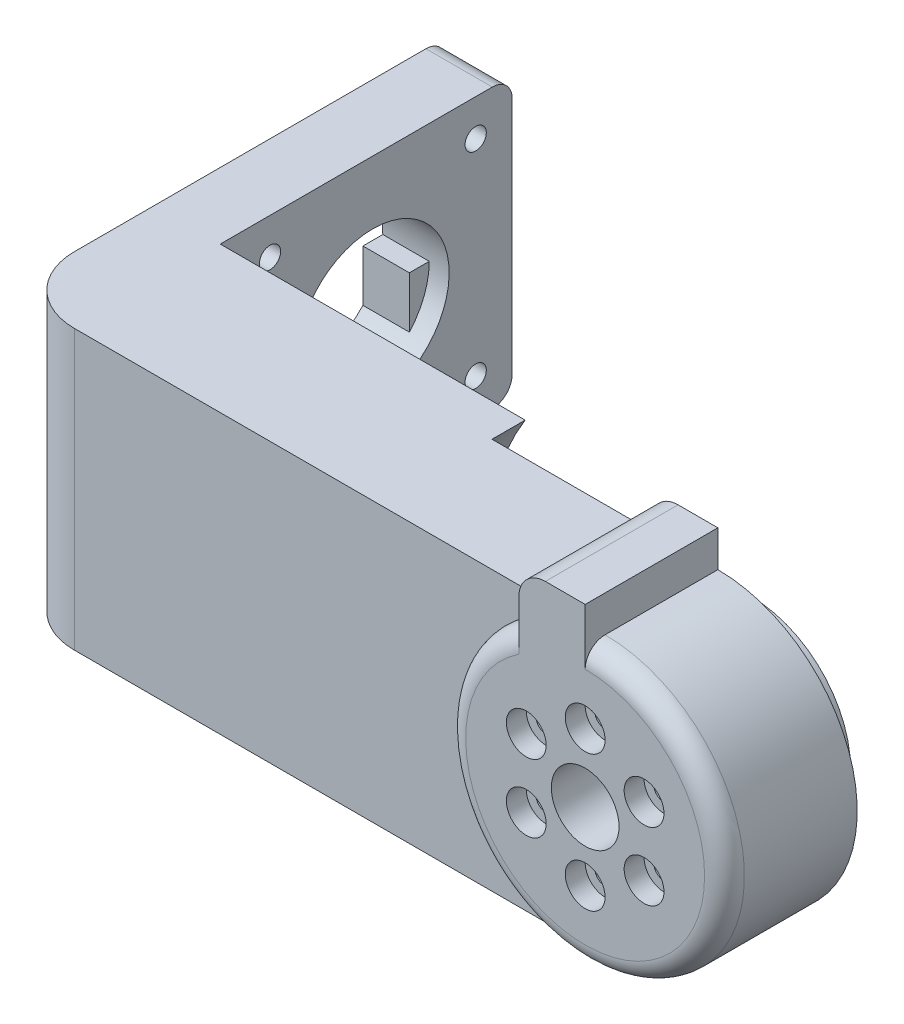
SolidWorks part; units mm, degrees
ref_plane "前视基准面" through (0, 0, 0) normal (0, 0, 1) x (1, 0, 0)
ref_plane "上视基准面" through (0, 0, 0) normal (0, 1, 0) x (1, 0, 0)
ref_plane "右视基准面" through (0, 0, 0) normal (1, 0, 0) x (0, 0, -1)
sketch "草图1" plane through (0, 0, 0) normal (0, 0, 1) x (1, 0, 0)
  line L1 (-45, 21) -> (45, 21)
  line L2 (-45, 21) -> (-45, -21)
  line L3 (-45, -21) -> (45, -21)
  line L4 (45, 21) -> (45, -21)
  line L5 (0, -21) -> (0, 21) construction
  line L6 (-45, 0) -> (45, 0) construction
  point P0 (0, 0)
  dimension "D1" = 90
  dimension "D2" = 42
extrude "凸台-拉伸1" add sketch "草图1" along normal blind 54
sketch "草图2" plane through (0, 0, 0) normal (0, 0, -1) x (-1, 0, 0)
  circle A0 centre (-45, 0) radius 21
  dimension "D1" = 42
extrude "凸台-拉伸2" add sketch "草图2" against normal up to surface (54 mm away) up to face at (0, 0, 54)
sketch "草图3" plane through (0, 0, 0) normal (0, 0, -1) x (-1, 0, 0)
  circle A0 centre (-45, 0) radius 40
  dimension "D1" = 80
extrude "切除-拉伸1" cut sketch "草图3" against normal offset from surface (49 mm away) 5 up to face at (5.25, 0, 54)
sketch "草图4" plane through (0, 0, 49) normal (0, 0, -1) x (-1, 0, 0)
  circle A0 centre (-45, 0) radius 15
  dimension "D1" = 30
extrude "凸台-拉伸3" add sketch "草图4" along normal blind 5
sketch "草图5" plane through (0, 0, 54) normal (0, 0, 1) x (1, 0, 0)
  circle A0 centre (45, 0) radius 21
  dimension "D1" = 42
extrude "凸台-拉伸4" add sketch "草图5" along normal blind 15
sketch "草图7" plane through (0, 0, 69) normal (0, 0, 1) x (1, 0, 0)
  line L0 (0, 0) -> (78.2042, 0) construction
  line L1 (45, 21) -> (45, -21) construction
  circle A0 centre (45, 0) radius 21 construction
  point P8 (45, 0)
sketch "草图10" plane through (0, 0, 0) normal (0, 0, -1) x (-1, 0, 0)
  line L0 (45, -21) -> (-10.9559, -21) construction
  line L1 (-10.9559, 21) -> (35, 21)
  line L2 (-10.9559, 21) -> (-10.9559, -21)
  line L3 (-10.9559, -21) -> (35, -21)
  line L4 (35, 21) -> (35, -21)
  line L5 (45, 21) -> (45, -21) construction
  dimension "D1" = 10
extrude "切除-拉伸2" cut sketch "草图10" against normal blind 44
sketch "草图11" plane through (0, 0, 69) normal (0, 0, 1) x (1, 0, 0)
  circle A0 centre (45, 0) radius 5.1
  circle A1 centre (45, 10.25) radius 1.55
  circle A2 centre (53.8768, 5.125) radius 1.55
  circle A3 centre (53.8768, -5.125) radius 1.55
  circle A4 centre (45, -10.25) radius 1.55
  circle A5 centre (36.1232, -5.125) radius 1.55
  circle A6 centre (36.1232, 5.125) radius 1.55
  point P17 (45, 0)
  dimension "D1" = 10.2
  dimension "D2" = 3.1
  dimension "D3" = 10.25
extrude "切除-拉伸3" cut sketch "草图11" against normal through all
sketch "草图12" plane through (0, 0, 69) normal (0, 0, 1) x (1, 0, 0)
  circle A0 centre (45, 10.25) radius 3
  circle A1 centre (53.8768, 5.125) radius 3
  circle A2 centre (53.8768, -5.125) radius 3
  circle A3 centre (45, -10.25) radius 3
  circle A4 centre (36.1232, -5.125) radius 3
  circle A5 centre (36.1232, 5.125) radius 3
  circle A6 centre (45, 0) radius 5 construction
  point P16 (45, 0)
  dimension "D1" = 6
extrude "切除-拉伸4" cut sketch "草图12" against normal blind 3
sketch "草图13" plane through (-35, 0, 0) normal (1, 0, 0) x (0, 0, -1)
  line L0 (-21, 20.3079) -> (-21, -23.4653) construction
  line L3 (-27.124, 0) -> (17.7973, 0) construction
  line L4 (-44, 21) -> (0, 21) construction
  line L5 (-44, -21) -> (0, -21) construction
  line L6 (0, -21) -> (0, 21) construction
  circle A0 centre (-21, 0) radius 11.5
  circle A1 centre (-5.5, 15.5) radius 1.6
  circle A2 centre (-5.5, -15.5) radius 1.6
  circle A3 centre (-36.5, -15.5) radius 1.6
  circle A4 centre (-36.5, 15.5) radius 1.6
  point P26 (-21, 0)
  dimension "D1" = 23
  dimension "D2" = 3.2
  dimension "D3" = 31
  dimension "D4" = 31
  dimension "D5" = 21
  dimension "D6" = 4
extrude "切除-拉伸5" cut sketch "草图13" against normal through all
fillet "圆角3" radius 3 2 edges at (-40, -21, 0) (-40, 21, 0)
sketch "草图14" plane through (-45, 0, 0) normal (-1, 0, 0) x (0, 0, 1)
  circle A0 centre (5.5, 15.5) radius 3.1
  circle A1 centre (36.5, 15.5) radius 3.1
  circle A2 centre (36.5, -15.5) radius 3.1
  circle A3 centre (5.5, -15.5) radius 3.1
  point P12 (21, 0)
  dimension "D1" = 6.2
extrude "切除-拉伸6" cut sketch "草图14" against normal blind 3
sketch "草图15" plane through (0, 0, 69) normal (0, 0, 1) x (1, 0, 0)
  line L5 (45, 21) -> (45, -21) construction
  line L6 (35, 18.4662) -> (45, 18.4662)
  line L7 (35, 18.4662) -> (35, 26.4662)
  line L8 (35, 26.4662) -> (45, 26.4662)
  line L9 (45, 18.4662) -> (45, 26.4662)
  circle A1 centre (45, 0) radius 21 construction
  dimension "D1" = 10
  dimension "D2" = 8
extrude "凸台-拉伸5" add sketch "草图15" against normal up to surface (20 mm away) up to face at (60, 0, 49)
fillet "圆角6" radius 3 1 edges at (50.158, -20.3567, 69)
fillet "圆角8" radius 4 1 edges at (35, 26.4662, 59)
sketch "草图16" plane through (0, 0, 54) normal (0, 0, 1) x (1, 0, 0)
  line L0 (-45, -21) -> (45, -21) construction
  line L1 (35, 21) -> (35, 18.4662) construction
  line L2 (35, 21) -> (-45, 21) construction
  line L3 (-45, -21) -> (45, -21)
  line L4 (35, 21) -> (35, 18.4662)
  line L5 (35, 21) -> (-45, 21)
  line L6 (-45, 21) -> (-45, -21) construction
  line L7 (-45, 21) -> (-45, -21)
  arc A0 (35, 18.4662) -> (45, -21) centre (45, 0) ccw construction
  arc A1 (35, 18.4662) -> (45, -21) centre (45, 0) ccw
extrude "凸台-拉伸6" add sketch "草图16" along normal blind 12
fillet "圆角9" radius 10 1 edges at (-45, 0, 66)
sketch "草图17" plane through (-45, 0, 0) normal (-1, 0, 0) x (0, 0, 1)
  line L0 (27.124, 0) -> (-17.7973, 0) construction
  line L1 (9.5, 0) -> (12.5, 0)
  line L2 (9.5, 0) -> (9.5, -7.746)
  line L3 (9.5, -7.746) -> (12.5, -7.746)
  line L4 (12.5, 0) -> (12.5, -7.746)
  circle A0 centre (21, 0) radius 11.5 construction
  circle A1 centre (21, 0) radius 11.5 construction
  dimension "D1" = 3
extrude "凸台-拉伸7" add sketch "草图17" against normal blind 7
